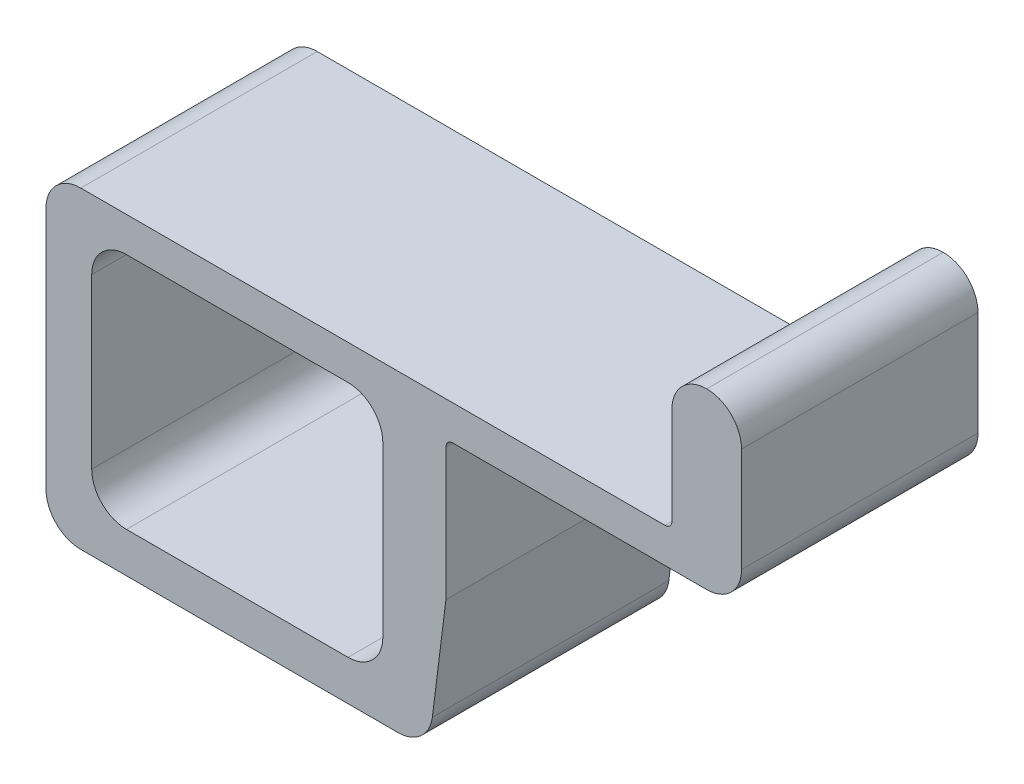
SolidWorks part; units mm, degrees
ref_plane "Front Plane" through (0, 0, 0) normal (0, 0, 1) x (1, 0, 0)
ref_plane "Top Plane" through (0, 0, 0) normal (0, 1, 0) x (1, 0, 0)
ref_plane "Right Plane" through (0, 0, 0) normal (1, 0, 0) x (0, 0, -1)
sketch "Sketch1" plane through (0, 0, 0) normal (0, 0, 1) x (1, 0, 0)
  line L0 (23.9819, 10.6109) -> (-16.0181, 10.6109)
  line L1 (-76.0181, 15.6109) -> (13.9819, 15.6109)
  line L2 (-76.0181, 15.6109) -> (-76.0181, 10.6109)
  line L3 (-16.0181, 10.6109) -> (23.9819, 10.6109)
  line L4 (23.9819, 15.6109) -> (23.9819, 10.6109)
  line L5 (-18.5181, -9.3891) -> (-18.5181, 10.6109)
  line L6 (-18.5181, 10.6109) -> (-16.0181, 10.6109)
  line L8 (-76.0181, 10.6109) -> (-76.0181, -29.3891)
  line L9 (-76.0181, -29.3891) -> (-21.0181, -29.3891)
  line L11 (-18.5181, -9.3891) -> (-21.0181, -29.3891)
  line L13 (-69.4475, -23.6093) -> (-27.5887, -23.6093)
  line L14 (-69.4475, -23.6093) -> (-69.4475, 10.6109)
  line L16 (23.9819, 15.6109) -> (23.9819, 35.6109)
  line L17 (23.9819, 35.6109) -> (13.9819, 35.6109)
  line L18 (13.9819, 15.6109) -> (13.9819, 35.6109)
  line L19 (-69.4475, 10.6109) -> (-27.5887, 10.6109)
  line L20 (-27.5887, -23.6093) -> (-27.5887, 10.6109)
  line L21 (-69.4475, -23.6093) -> (-27.5887, 10.6109) construction
  line L22 (-69.4475, 10.6109) -> (-27.5887, -23.6093) construction
  point P0 (-26.0181, 25.6109)
  point P13 (-48.5181, -6.4992)
  dimension "D1" = 100
  dimension "D2" = 5
  dimension "D3" = 40
  dimension "D4" = 55
extrude "Boss-Extrude1" add sketch "Sketch1" along normal blind 34 contours L18 L1 L2 L8 L9 L11 L0 L4 L16 L17 region at (3.9819, 11.8035, 0)
fillet "Fillet1" radius 1 2 edges at (-18.5181, 10.6109, 17) (13.9819, 15.6109, 17)
fillet "Fillet2" radius 5 4 edges at (-69.4475, -23.6093, 17) (-27.5887, -23.6093, 17) (-27.5887, 10.6109, 17) (-69.4475, 10.6109, 17)
fillet "Fillet3" radius 5 6 edges at (13.9819, 35.6109, 17) (23.9819, 35.6109, 17) (23.9819, 10.6109, 17) (-76.0181, 15.6109, 17) (-76.0181, -29.3891, 17) (-21.0181, -29.3891, 17)
